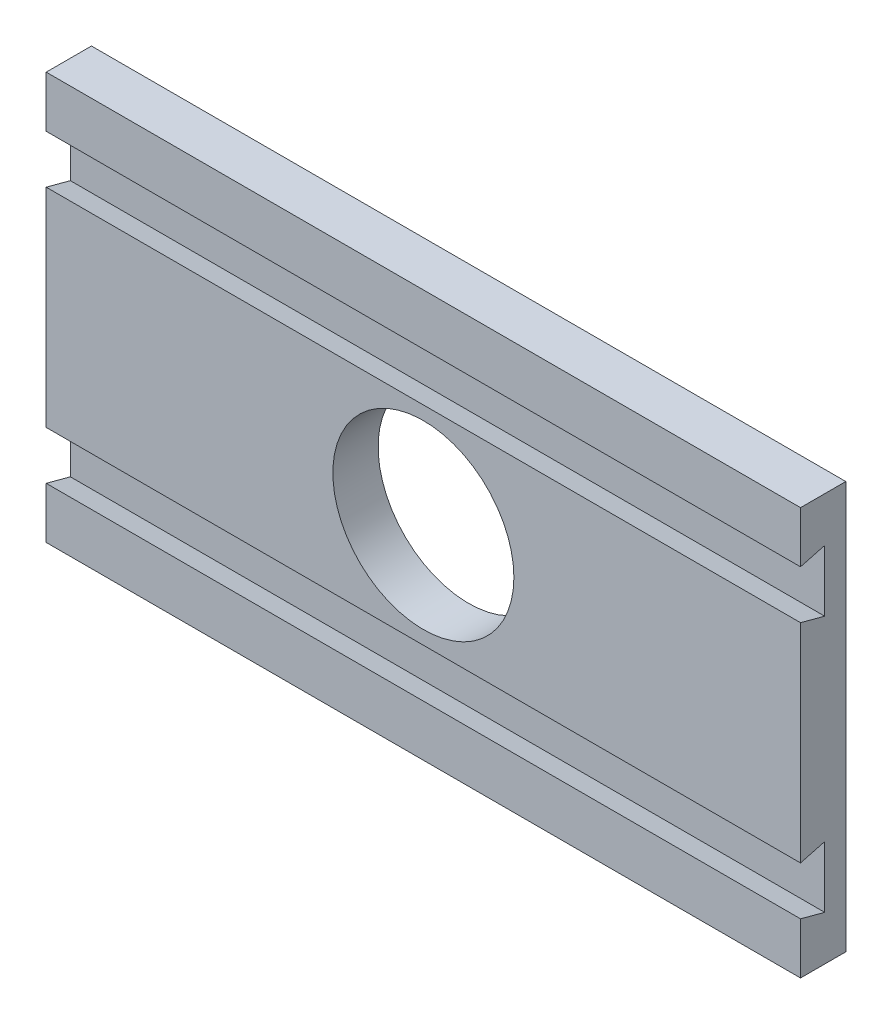
SolidWorks part; units mm, degrees
ref_plane "Front Plane" through (0, 0, 0) normal (0, 0, 1) x (1, 0, 0)
ref_plane "Top Plane" through (0, 0, 0) normal (0, 1, 0) x (1, 0, 0)
ref_plane "Right Plane" through (0, 0, 0) normal (1, 0, 0) x (0, 0, -1)
sketch "Plate profile" plane through (0, 0, 0) normal (0, 0, 1) x (1, 0, 0)
  line L0 (-50, -27) -> (50, -27)
  line L1 (50, -27) -> (50, 27)
  line L2 (50, 27) -> (-50, 27)
  line L3 (-50, 27) -> (-50, -27)
  circle A0 centre (0, 0) radius 12
extrude "Plate 6mm" add sketch "Plate profile" against normal blind 6
sketch "Groove profiles" plane through (0, 0, 0) normal (1, 0, 0) x (0, 0, -1)
  line L0 (-0.2, 13.8463) -> (3.2, 12.9397)
  line L1 (3.2, 12.9397) -> (3.2, 21.0603)
  line L2 (3.2, 21.0603) -> (-0.2, 20.1537)
  line L3 (-0.2, 20.1537) -> (-0.2, 13.8463)
  line L4 (-0.2, -13.8463) -> (3.2, -12.9397)
  line L5 (3.2, -12.9397) -> (3.2, -21.0603)
  line L6 (3.2, -21.0603) -> (-0.2, -20.1537)
  line L7 (-0.2, -20.1537) -> (-0.2, -13.8463)
extrude "Dovetail grooves" cut sketch "Groove profiles" against normal through all both and the other way through all
